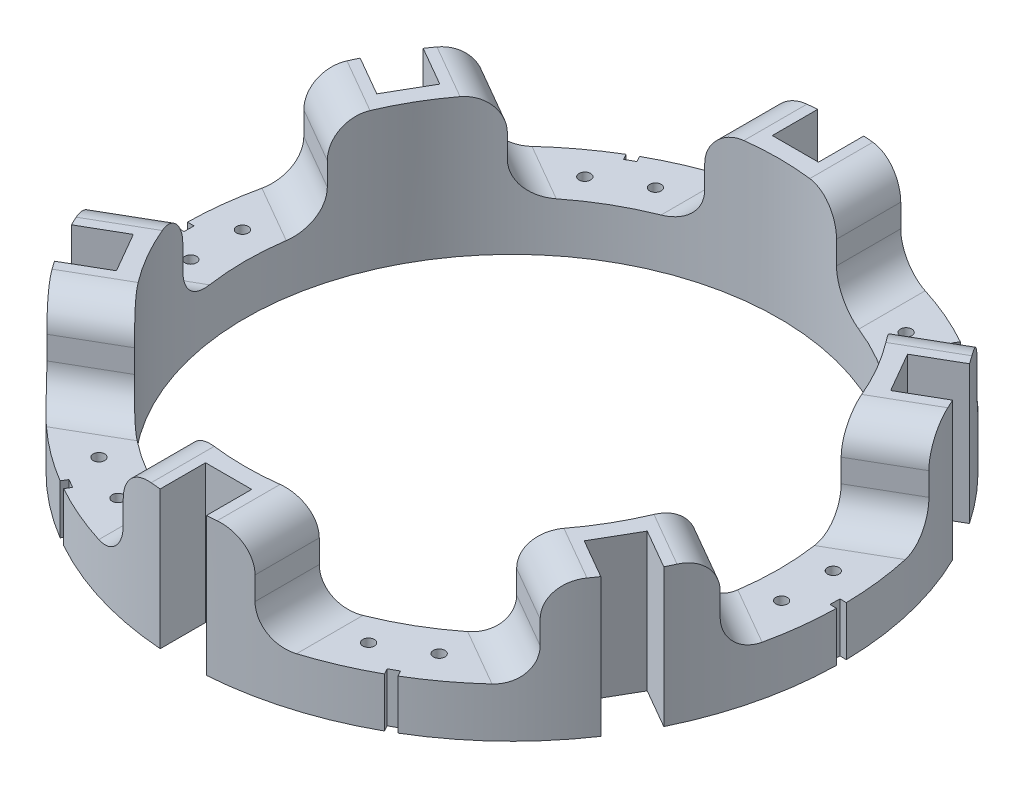
SolidWorks part; units mm, degrees
ref_plane "Спереди" through (0, 0, 0) normal (0, 0, 1) x (1, 0, 0)
ref_plane "Сверху" through (0, 0, 0) normal (0, 1, 0) x (1, 0, 0)
ref_plane "Справа" through (0, 0, 0) normal (1, 0, 0) x (0, 0, -1)
sketch "Эскиз1" plane through (0, 0, 0) normal (0, 1, 0) x (1, 0, 0)
  circle A0 centre (0, 0) radius 81
  circle A1 centre (0, 0) radius 100
  dimension "D1" = 200
  dimension "D2" = 162
extrude "Бобышка-Вытянуть1" add sketch "Эскиз1" along normal blind 15
sketch "Эскиз2" plane through (0, 15, 0) normal (0, 1, 0) x (1, 0, 0)
  line L0 (0, 0) -> (0, 93) construction
  line L1 (-7, 100) -> (7, 100)
  line L2 (-7, 100) -> (-7, 86)
  line L3 (-7, 86) -> (7, 86)
  line L4 (7, 100) -> (7, 86)
  line L5 (-7, 100) -> (7, 86) construction
  line L6 (-7, 86) -> (7, 100) construction
  circle A0 centre (0, 0) radius 100 construction
  point P0 (0, 93)
  dimension "D1" = 14
  dimension "D2" = 14
ref_plane "Плоскость1" through (0, 0, -100) normal (0, 0, -1) x (-1, 0, 0)
sketch "Эскиз5" plane through (0, 15, 0) normal (0, 1, 0) x (1, 0, 0)
  line L0 (-20, 78.492) -> (-20, 97.9796)
  line L1 (20, 78.492) -> (20, 97.9796)
  line L3 (0, 93) -> (-20, 93) construction
  line L4 (-7, 100) -> (7, 86) construction
  line L5 (0, 93) -> (20, 93) construction
  arc A0 (-20, 78.492) -> (20, 78.492) centre (0, 0) cw
  circle A1 centre (0, 0) radius 81 construction
  arc A2 (-20, 97.9796) -> (20, 97.9796) centre (0, 0) cw
  circle A3 centre (0, 0) radius 100 construction
  dimension "D1" = 40
extrude "Бобышка-Вытянуть2" add sketch "Эскиз5" along normal blind 27
extrude "Вырез-Вытянуть2" cut sketch "Эскиз2" along normal through all and the other way through all contours L3 L4 L1 L2
fillet "Скругление1" radius 10 4 edges at (-20, 15, -88.2358) (-20, 42, -88.2358) (20, 15, -88.2358) (20, 42, -88.2358)
pattern_circular "Круговой массив2" count 6 over 360 about axis through (0, 15, 0) along (0, 1, 0) of "Скругление1", "Вырез-Вытянуть2", "Бобышка-Вытянуть2"
sketch "Эскиз6" plane through (0, 15, 0) normal (0, 1, 0) x (1, 0, 0)
  line L0 (0, 0) -> (-45, 77.9423) construction
  line L1 (0, 0) -> (0, 93) construction
  line L2 (-45, 77.9423) -> (-49.0057, 84.8804) construction
  line L3 (-50.3161, 84.1504) -> (-47.6954, 85.6105)
  line L4 (-51.2895, 85.8976) -> (-48.6688, 87.3576)
  line L5 (-50.3161, 84.1504) -> (-51.2895, 85.8976)
  line L6 (-47.6954, 85.6105) -> (-48.6688, 87.3576)
  line L7 (0, 0) -> (-38.0356, 81.5677) construction
  line L8 (0, 0) -> (-51.6219, 73.7237) construction
  circle A0 centre (0, 0) radius 90 construction
  arc A2 (-30, 95.3939) -> (-67.6136, 73.6777) centre (0, 0) ccw construction
  circle A3 centre (-51.6219, 73.7237) radius 1.75
  circle A4 centre (-38.0356, 81.5677) radius 1.75
  point P14 (-49.0057, 84.8804)
  point P17 (-49.9791, 86.6276)
  dimension "D1" = 180
  dimension "D3" = 10
  dimension "D7" = 3.5
  dimension "D8" = 3.5
  dimension "D2" = 30
  dimension "D4" = 3
  dimension "D5" = 2
  dimension "D6" = 5
extrude "Вырез-Вытянуть3" cut sketch "Эскиз6" against normal through all
pattern_circular "Круговой массив3" count 6 over 360 about axis through (0, 15, 0) along (0, 1, 0) of "Вырез-Вытянуть3"
